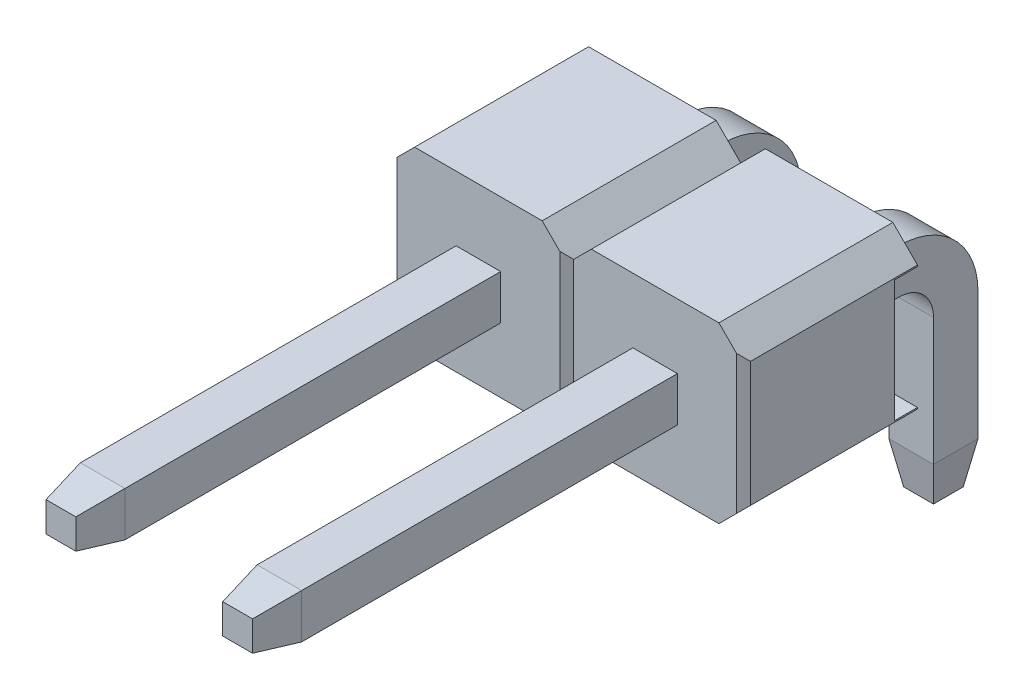
SolidWorks part; units mm, degrees
ref_plane "Front Plane" through (0, 0, 0) normal (0, 0, 1) x (1, 0, 0)
ref_plane "Top Plane" through (0, 0, 0) normal (0, 1, 0) x (1, 0, 0)
ref_plane "Right Plane" through (0, 0, 0) normal (1, 0, 0) x (0, 0, -1)
sketch "Sketch1" plane through (0, 0, 0) normal (0, 0, 1) x (1, 0, 0)
  line L0 (-1.27, 0.8964) -> (-0.9164, 1.25)
  line L1 (-0.9164, 1.25) -> (0.9164, 1.25)
  line L2 (-1.27, 0.8964) -> (-1.27, -0.8964)
  line L3 (-0.9164, -1.25) -> (0.9164, -1.25)
  line L4 (1.27, 0.8964) -> (1.27, -0.8964)
  line L5 (-1.27, -0.8964) -> (-0.9164, -1.25)
  line L6 (0.9164, -1.25) -> (1.27, -0.8964)
  line L7 (1.27, 0.8964) -> (0.9164, 1.25)
  point P0 (1.27, -1.25)
  point P7 (-1.27, 1.25)
  point P10 (-1.27, -1.25)
  point P15 (1.27, 1.25)
  dimension "D5" = 0.25
  dimension "D1" = 2.54
  dimension "D2" = 2.5
  dimension "D3" = 1.27
  dimension "D4" = 1.25
  dimension "D6" = 0.25
  dimension "D7" = 0.25
  dimension "D8" = 0.25
extrude "Extrude1" add sketch "Sketch1" along normal blind 1.25 and the other way blind 1.25
sketch "Sketch4" plane through (0, 0, 0) normal (0, 1, 0) x (1, 0, 0)
  line L0 (-1.27, -1.15) -> (-1.17, -1.25)
  line L1 (-1.17, -1.25) -> (-1.27, -1.25)
  line L2 (-1.27, -1.25) -> (-1.27, -1.15)
  line L3 (1.17, -1.25) -> (1.27, -1.15)
  line L4 (1.27, -1.15) -> (1.27, -1.25)
  line L5 (1.27, -1.25) -> (1.17, -1.25)
extrude "Cut-Extrude3" cut sketch "Sketch4" against normal through all and the other way through all
pattern_linear "LPattern4" count 2 spacing 2.54 along (-1, 0, 0) of "Extrude1", "Cut-Extrude3"
sketch "Sketch2" plane through (0, 0, 0) normal (1, 0, 0) x (0, -1, 0)
  line L1 (-0.8764, 1.25) -> (0.8764, 1.25)
  line L2 (-0.8764, 1.25) -> (-0.8764, 0.92)
  line L3 (-0.8764, 0.92) -> (0.8764, 0.92)
  line L4 (0.8764, 1.25) -> (0.8764, 0.92)
  dimension "D1" = 0.33
extrude "Cut-Extrude1" cut sketch "Sketch2" against normal through all and the other way through all
sketch "Sketch3" plane through (0, 0, 0) normal (1, 0, 0) x (0, 0, -1)
  line L0 (-7.25, 0) -> (2.75, 0)
  line L1 (2.75, 0) -> (2.75, -3.25)
  line L2 (-1.25, -1.25) -> (1.25, -1.25) construction
  line L3 (1.25, 1.25) -> (1.25, 0.8964) construction
  dimension "D1" = 6
  dimension "D2" = 1.5
  dimension "D3" = 2
extrude "Extrude-Thin1" add sketch "Sketch3" along normal blind 0.32 and the other way blind 0.32 thin thin type mid plane wall 0.64
pattern_linear "LPattern5" count 1 spacing 2.54 along (1, 0, 0) count 2 spacing 2.54 along (-1, 0, 0) of "Extrude-Thin1"
chamfer "Chamfer2" distance 0.6 angle 10 16 edges at (0.32, 0, 7.25) (0, -0.32, 7.25) (-0.32, 0, 7.25) (0, 0.32, 7.25) (0.32, -3.25, -2.75) (0, -3.25, -3.07) (-0.32, -3.25, -2.75) (0, -3.25, -2.43) (-2.22, -3.25, -2.75) (-2.54, -3.25, -3.07) (-2.86, -3.25, -2.75) (-2.54, -3.25, -2.43) (-2.22, 0, 7.25) (-2.54, -0.32, 7.25) (-2.86, 0, 7.25) (-2.54, 0.32, 7.25) first distance on face at (0.32, 0, 4.25) first distance on face at (0, -0.32, 4.25) first distance on face at (-0.32, 0, 4.25) first distance on face at (0, 0.32, 4.25) first distance on face at (0.32, -1.0833, -2.14) first distance on face at (0, -1.465, -3.07) first distance on face at (-0.32, -1.0833, -2.14) first distance on face at (0, -1.785, -2.43) first distance on face at (-2.22, -1.0833, -2.14) first distance on face at (-2.54, -1.465, -3.07) first distance on face at (-2.86, -1.0833, -2.14) first distance on face at (-2.54, -1.785, -2.43) first distance on face at (-2.22, 0, 4.25) first distance on face at (-2.54, -0.32, 4.25) first distance on face at (-2.86, 0, 4.25) first distance on face at (-2.54, 0.32, 4.25)
fillet "Fillet1" radius 0.5 2 edges at (0, -0.32, -2.43) (-2.54, -0.32, -2.43)
fillet "Fillet2" radius 1.14 2 edges at (0, 0.32, -3.07) (-2.54, 0.32, -3.07)
ref_plane "Board Plane" through (0, -1.5, 0) normal (0, 1, 0) x (-1, 0, 0)
sketch "Component_Outline" plane through (0, -1.5, 0) normal (0, 1, 0) x (-1, 0, 0)
  line L0 (3.71, 1.25) -> (3.81, 1.15)
  line L1 (3.81, 1.15) -> (3.81, -1.25)
  line L2 (3.81, -1.25) -> (2.86, -1.25)
  line L3 (3.4564, -1.25) -> (1.6236, -1.25) construction
  line L4 (2.86, -0.92) -> (2.86, -1.93) construction
  line L5 (2.86, -1.25) -> (2.86, -3.07)
  line L6 (2.86, -3.07) -> (-0.32, -3.07)
  line L7 (-0.32, -3.07) -> (-0.32, -1.25)
  line L8 (-0.32, -0.92) -> (-0.32, -1.93) construction
  line L9 (0.9164, -1.25) -> (-0.9164, -1.25) construction
  line L10 (-0.32, -1.25) -> (-1.27, -1.25)
  line L11 (-1.27, -1.25) -> (-1.27, 1.15)
  line L12 (-1.27, 1.15) -> (-1.17, 1.25)
  line L13 (-1.17, 1.25) -> (1.17, 1.25)
  line L14 (1.17, 1.25) -> (1.27, 1.15)
  line L15 (1.27, 1.15) -> (1.37, 1.25)
  line L16 (1.37, 1.25) -> (3.71, 1.25)
  line L17 (-0.2142, -2.9642) -> (0.2142, -2.5358) construction
  line L21 (-0.2142, -2.9642) -> (0.2142, -2.9642)
  line L22 (-0.2142, -2.5358) -> (-0.2142, -2.9642)
  line L23 (0.2142, -2.5358) -> (-0.2142, -2.5358)
  line L24 (0.2142, -2.9642) -> (0.2142, -2.5358)
  line L25 (-0.2142, -2.9642) -> (0.2142, -2.9642) construction
  line L26 (-0.2142, -2.5358) -> (-0.2142, -2.9642) construction
  line L27 (0.2142, -2.5358) -> (-0.2142, -2.5358) construction
  line L28 (0.2142, -2.9642) -> (0.2142, -2.5358) construction
  point P34 (0, -2.75)
  dimension "D1" = 0
